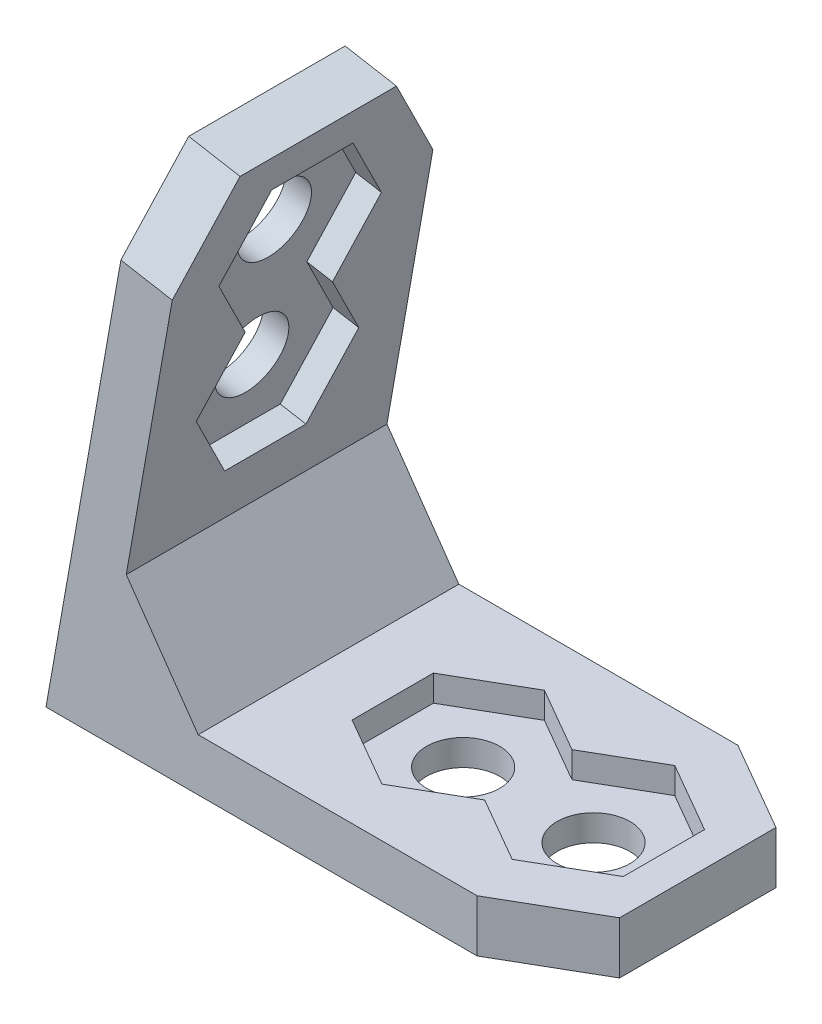
SolidWorks part; units mm, degrees
ref_plane "Front Plane" through (0, 0, 0) normal (0, 0, 1) x (1, 0, 0)
ref_plane "Top Plane" through (0, 0, 0) normal (0, 1, 0) x (1, 0, 0)
ref_plane "Right Plane" through (0, 0, 0) normal (1, 0, 0) x (0, 0, -1)
sketch "Sketch1" plane through (0, 0, 0) normal (0, 1, 0) x (1, 0, 0)
  line L1 (0, 0) -> (25.4, 0)
  line L2 (0, 0) -> (0, -12.7)
  line L3 (0, -12.7) -> (25.4, -12.7)
  line L4 (25.4, 0) -> (25.4, -12.7)
  dimension "D1" = 25.4
  dimension "D2" = 12.7
extrude "Boss-Extrude1" add sketch "Sketch1" along normal blind 2.54 contours L1 L4 L3 L2
sketch "Sketch2" plane through (0, 2.54, 0) normal (0, 1, 0) x (1, 0, 0)
  line L0 (0, -6.35) -> (25.4, -6.35) construction
  line L1 (0, 0) -> (0, -12.7) construction
  line L2 (25.4, 0) -> (25.4, -12.7) construction
  circle A0 centre (13.97, -6.35) radius 1.778
  circle A1 centre (20.32, -6.35) radius 1.778
  dimension "D2" = 3.556
  dimension "D1" = 6.35
  dimension "D3" = 5.08
extrude "Cut-Extrude1" cut sketch "Sketch2" against normal through all contours A1 L0 | L0 A1 | L0 A0 | A0 L0 region at (13.97, 2.54, 5.5954) region at (20.32, 2.54, 5.5954) region at (20.32, 2.54, 7.1046) region at (13.97, 2.54, 7.1046)
sketch "Sketch4" plane through (0, 2.54, 0) normal (0, 1, 0) x (1, 0, 0)
  line L1 (13.97, -2.3905) -> (10.541, -4.3703)
  line L2 (10.541, -4.3703) -> (10.541, -8.3297)
  line L3 (10.541, -8.3297) -> (13.97, -10.3095)
  line L4 (13.97, -10.3095) -> (17.399, -8.3297)
  line L5 (17.399, -8.3297) -> (17.399, -4.3703)
  line L6 (17.399, -4.3703) -> (13.97, -2.3905)
  line L7 (20.32, -2.3905) -> (16.891, -4.3703)
  line L8 (16.891, -4.3703) -> (16.891, -8.3297)
  line L9 (16.891, -8.3297) -> (20.32, -10.3095)
  line L10 (20.32, -10.3095) -> (23.749, -8.3297)
  line L11 (23.749, -8.3297) -> (23.749, -4.3703)
  line L12 (23.749, -4.3703) -> (20.32, -2.3905)
  circle A0 centre (13.97, -6.35) radius 3.429 construction
  circle A1 centre (20.32, -6.35) radius 3.429 construction
  circle M13 centre (20.32, -6.35) radius 1.778
  circle M14 centre (13.97, -6.35) radius 1.778
  dimension "D1" = 6.858
chamfer "Chamfer1" distance 2.54 angle 50 1 edges at (0, 2.54, 6.35) first distance on face at (0, 1.27, 6.35)
extrude "Cut-Extrude2" cut sketch "Sketch4" against normal blind 1.27 contours L9 L8 L7 L6 L1 L2 L3 L4 M14 | L11 L12 L7 L6 L5 L4 L9 L10 M13 | L8 L9 L4 L5 L6 L7 region at (15.5059, 2.54, 3.3964) region at (18.7841, 2.54, 3.3964) region at (17.145, 2.54, 6.35)
chamfer "Chamfer3" distance 2.54 angle 60 2 edges at (25.4, 1.27, 0) (25.4, 1.27, 12.7) first distance on face at (25.4, 1.27, 6.35)
mirror "Mirror1" about plane through (3.0271, 2.54, 0) normal (-0.6428, 0.766, 0) of bodies 105 103
chamfer "Chamfer2" distance 5.08 angle 45 1 edges at (3.0271, 2.54, 6.35) first distance on face at (5.4786, 16.4435, 6.35)
equation "\"D1@Chamfer1\"=\"D1@Boss-Extrude1\""
